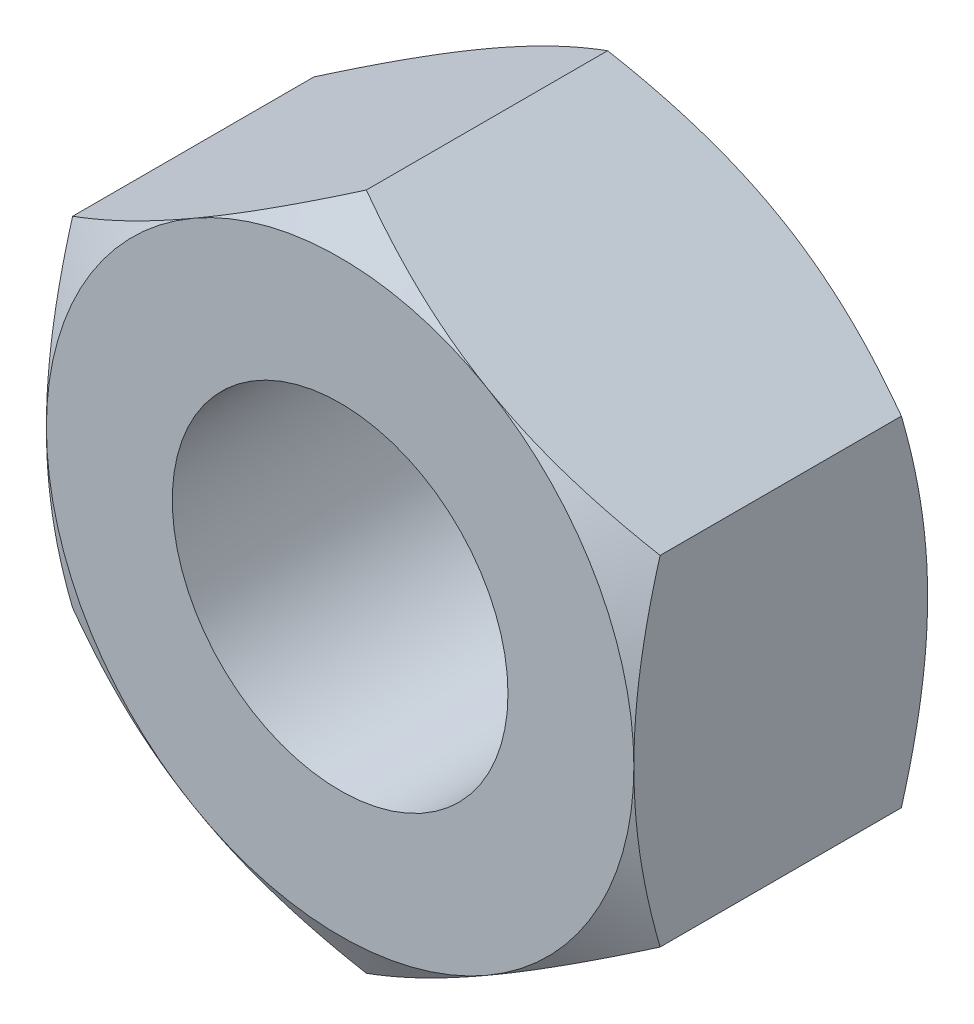
SolidWorks part; units mm, degrees
ref_plane "Front" through (0, 0, 0) normal (0, 0, 1) x (1, 0, 0)
ref_plane "Top" through (0, 0, 0) normal (0, 1, 0) x (1, 0, 0)
ref_plane "Right" through (0, 0, 0) normal (1, 0, 0) x (0, 0, -1)
sketch "Sketch1" plane through (0, 0, 0) normal (0, 0, 1) x (1, 0, 0)
  line L1 (-5.5562, 3.2079) -> (-5.5562, -3.2079)
  line L2 (-5.5562, -3.2079) -> (0, -6.4158)
  line L3 (0, -6.4158) -> (5.5562, -3.2079)
  line L4 (5.5562, -3.2079) -> (5.5562, 3.2079)
  line L5 (5.5562, 3.2079) -> (0, 6.4158)
  line L6 (0, 6.4158) -> (-5.5562, 3.2079)
  circle A0 centre (0, 0) radius 5.5562 construction
  circle A1 centre (0, 0) radius 3.175
  point P10 (0, 3.175)
  dimension "hex" = 11.1125
  dimension "dia" = 6.35
extrude "Extrude1" add sketch "Sketch1" along normal mid plane 5.5562
sketch "Sketch4" plane through (0, 0, -2.7781) normal (0, 0, -1) x (-1, 0, 0)
  circle A0 centre (0, 0) radius 3.175 construction
  circle A1 centre (0, 0) radius 3.175
curve "Helix/Spiral3" [suppressed] pitch 1.27 height 6.6675 turns 5.25
sketch "Sketch3" plane through (0, 0, 0) normal (1, 0, 0) x (0, 0, -1)
  line L0 (2.7781, 3.175) -> (3.8894, 3.175)
  line L1 (3.8894, 3.175) -> (3.4131, 2.3501)
  line L2 (3.4131, 2.3501) -> (3.2544, 2.3501)
  line L3 (3.2544, 2.3501) -> (2.7781, 3.175)
  line L4 (3.0162, 2.7626) -> (3.6513, 2.7626) construction
  dimension "D1" = 60
  dimension "D2" = 0.635
  dimension "D3" = 0.1588
sweep "Sweep1" [suppressed] add profiles "Sketch3" path "Helix/Spiral3"
sketch "Sketch6" [suppressed] plane through (0, 0, 0) normal (1, 0, 0) x (0, 0, -1)
  line L0 (-3.0956, 3.4925) -> (-2.4606, 2.8575)
  line L1 (-2.4606, 2.8575) -> (-2.4606, 0) construction
  line L2 (3.9291, 0) -> (-3.9291, 0) construction
  line L3 (-2.4606, 0) -> (-3.8894, 0)
  line L4 (-3.8894, 0) -> (-3.8894, 3.4925)
  line L5 (-3.8894, 3.4925) -> (-3.0956, 3.4925)
  line L6 (-2.4606, 2.8575) -> (0.3969, 0)
  line L7 (0.3969, 0) -> (-2.4606, 0)
  line L8 (-2.7781, -3.2079) -> (-2.7781, 3.2079) construction
  point P2 (-2.7781, 3.175)
  dimension "D2" = 0.635
  dimension "D1" = 45
revolve "Cut-Revolve1" [suppressed] cut sketch "Sketch6" angle 360 about L3
sketch "Sketch7" plane through (0, 0, 2.7781) normal (0, 0, 1) x (1, 0, 0)
  circle A0 centre (0, 0) radius 5.5562 construction
  circle A1 centre (0, 0) radius 5.5562
extrude "Extrude2" cut sketch "Sketch7" against normal blind 25.4 draft 60 flip side to cut
mirror "Mirror1" about plane through (0, 0, 0) normal (0, 0, 1) of "Extrude2", "Cut-Revolve1"
sketch "Sketch8" [suppressed] plane through (0, 0, 2.7781) normal (0, 0, 1) x (1, 0, 0)
  line L0 (-2.2451, 2.2451) -> (0, 0) construction
  line L1 (0, -3.9291) -> (0, 3.9291) construction
  circle A0 centre (0, 0) radius 3.175 construction
  point P0 (-2.2451, 2.2451)
  dimension "D1" = 45
equation "\"D3@Helix/Spiral3\" = \"length@Extrude1\" * 1.2"
equation "\"D2@Sketch3\" = \"D4@Helix/Spiral3\" * .5"
equation "\"D3@Sketch3\" = \"D4@Helix/Spiral3\" * .125"
equation "\"D2@Sketch6\" = \"D4@Helix/Spiral3\" * .5"
